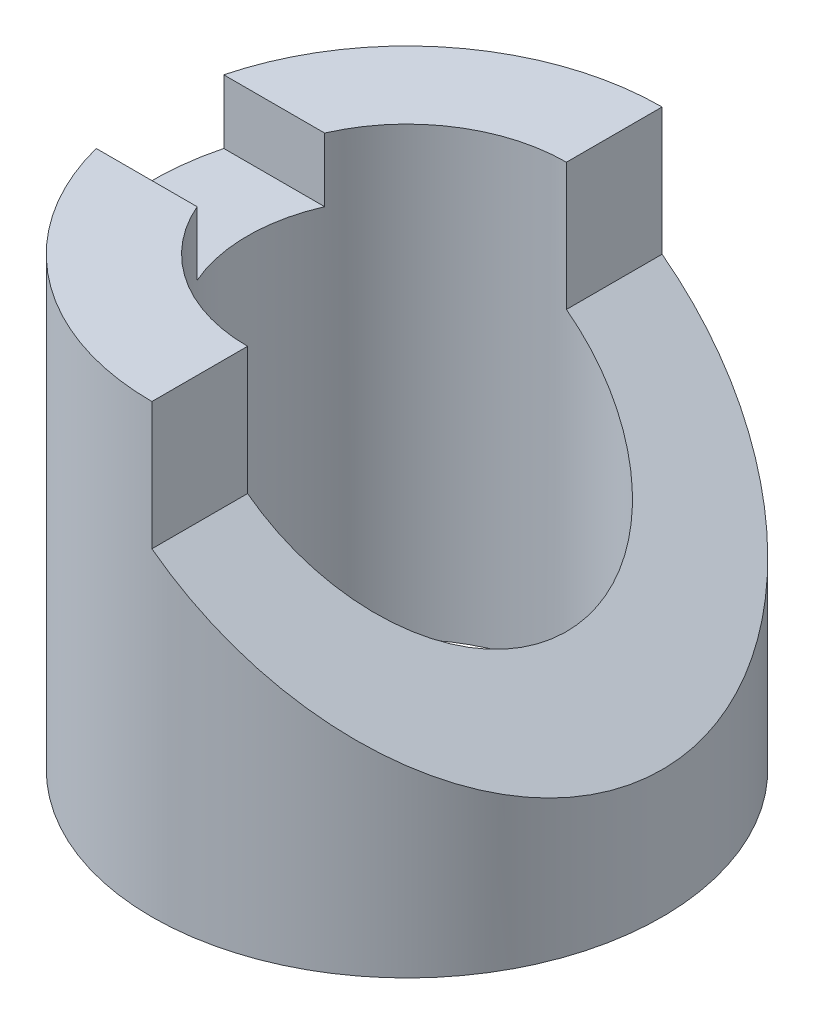
SolidWorks part; units mm, degrees
material "Nickel"
ref_plane "Front Plane" through (0, 0, 0) normal (0, 0, 1) x (1, 0, 0)
ref_plane "Top Plane" through (0, 0, 0) normal (0, 1, 0) x (1, 0, 0)
ref_plane "Right Plane" through (0, 0, 0) normal (1, 0, 0) x (0, 0, -1)
sketch "Sketch1" plane through (0, 0, 0) normal (0, 1, 0) x (1, 0, 0)
  line L0 (0, 40) -> (0, -40) construction
  line L1 (-40, 0) -> (40, 0) construction
  line L2 (0, 40) -> (0, -40)
  line L4 (-57.0871, 10) -> (-22.9129, 10)
  line L5 (-57.0871, 10) -> (-57.0871, -10)
  line L6 (-57.0871, -10) -> (-22.9129, -10)
  line L8 (-57.0871, 10) -> (-22.9129, -10) construction
  line L9 (-57.0871, -10) -> (-22.9129, 10) construction
  circle A0 centre (0, 0) radius 40
  circle A1 centre (0, 0) radius 25
  point P12 (-22.6142, 10.6583)
  dimension "D1" = 80
  dimension "D2" = 50
  dimension "D3" = 20
  dimension "D4" = 10
extrude "Boss-Extrude1" add sketch "Sketch1" along normal blind 70 contours A1 L2 A0 | A1 L6 A0 L2 | A1 L2 A0 L4 region at (27.6518, 0, -27.6518) region at (-18.3484, 0, -25.0438) region at (-18.3484, 0, 25.0438)
extrude "Boss-Extrude2" add sketch "Sketch1<3>" along normal blind 60 contours A1 L4 A0 L6 region at (-31.94, 0, 0)
sketch "Sketch1<3>" plane through (0, 0, 0) normal (0, 1, 0) x (1, 0, 0) same geometry as "Sketch1"
sketch "Sketch4" plane through (0, 0, 0) normal (0, 0, 1) x (1, 0, 0)
  line L0 (-40, 60) -> (-40, 0) construction
  line L1 (-40, 0) -> (40, 0) construction
  line L2 (40, 70) -> (-38.7298, 70) construction
  line L3 (40, 0) -> (40, 70) construction
  line L4 (-40, 50) -> (-40, 0)
  line L5 (-40, 0) -> (40, 0)
  line L6 (40, 70) -> (0, 70)
  line L7 (40, 0) -> (40, 70)
  line L8 (-40, 50) -> (40, 50)
  line L9 (0, 0) -> (0, 50)
  line L10 (0, 50) -> (40, 20)
  line L11 (0, 50) -> (0, 70)
  point P7 (40, 20)
  dimension "D1" = 20
  dimension "D2" = 20
extrude "Cut-Extrude1" cut sketch "Sketch4" against normal through all both and the other way through all contours L8 L10 L7 | L11 L8 L7 L6 region at (20, 60, 0) region at (26.6667, 40, 0)
